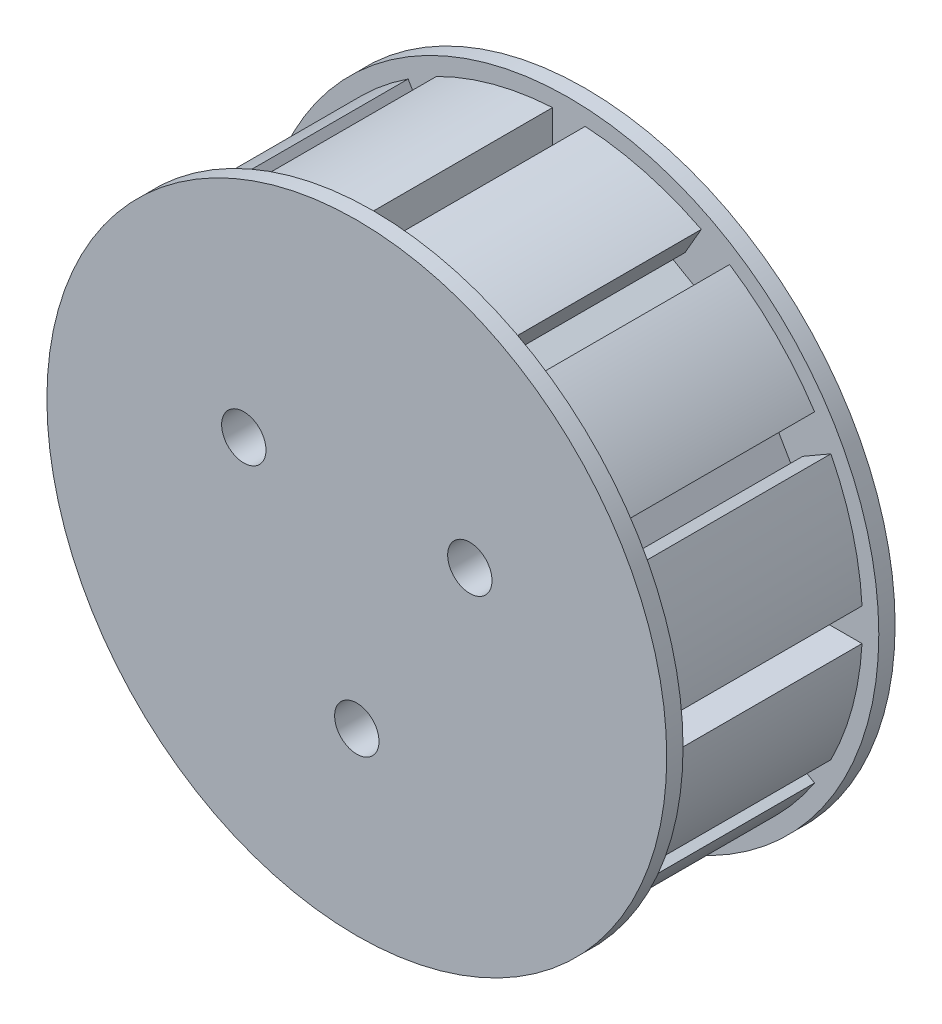
SolidWorks part; units mm, degrees
ref_plane "Front Plane" through (0, 0, 0) normal (0, 0, 1) x (1, 0, 0)
ref_plane "Top Plane" through (0, 0, 0) normal (0, 1, 0) x (1, 0, 0)
ref_plane "Right Plane" through (0, 0, 0) normal (1, 0, 0) x (0, 0, -1)
sketch "Sketch1" plane through (0, 0, 0) normal (0, 0, 1) x (1, 0, 0)
  circle A0 centre (0, 0) radius 28.575
  dimension "D1" = 57.15
extrude "Boss-Extrude1" add sketch "Sketch1" along normal mid plane 19.05
sketch "Sketch2" plane through (0, 0, 0) normal (0, 0, 1) x (1, 0, 0)
  line L0 (-1.5875, 28.5309) -> (-1.5875, 25.3559)
  line L1 (-1.5875, 25.3559) -> (-4.7625, 25.3559)
  line L2 (-4.7625, 25.3559) -> (-4.7625, 23.7684)
  line L3 (-4.7625, 23.7684) -> (4.7625, 23.7684)
  line L4 (4.7625, 23.7684) -> (4.7625, 25.3559)
  line L5 (4.7625, 25.3559) -> (1.5875, 25.3559)
  line L6 (1.5875, 25.3559) -> (1.5875, 28.5309)
  circle A0 centre (0, 0) radius 28.575 construction
  arc A1 (1.5875, 28.5309) -> (-1.5875, 28.5309) centre (0, 0) ccw
  point P11 (0, 23.7684)
  dimension "D1" = 9.525
  dimension "D2" = 3.175
  dimension "D3" = 3.175
  dimension "D4" = 1.5875
extrude "Cut-Extrude1" cut sketch "Sketch2" against normal mid plane 19.05
pattern_circular "CirPattern1" count 12 over 360 about axis through (0, 0, 9.525) along (0, 0, 1) of "Cut-Extrude1"
sketch "Sketch3" plane through (0, 0, -9.525) normal (0, 0, -1) x (-1, 0, 0)
  circle A0 centre (0, 0) radius 30.1625
  arc A1 (-25.5022, 12.8906) -> (-28.5309, 1.5875) centre (0, 0) ccw construction
  dimension "D1" = 1.5875
extrude "Boss-Extrude2" add sketch "Sketch3" along normal blind 1.5875
mirror "Mirror1" about plane through (0, 0, 0) normal (0, 0, 1) of "Boss-Extrude2"
sketch "Sketch4" plane through (0, 0, -11.1125) normal (0, 0, -1) x (-1, 0, 0)
  circle A0 centre (0, -12.7) radius 2.159
  circle A1 centre (-10.9985, 6.35) radius 2.159
  circle A2 centre (10.9985, 6.35) radius 2.159
  point P4 (-13.2921, 7.7818)
  point P5 (0, 0)
  point P9 (0, 0)
  dimension "D1" = 4.318
  dimension "D2" = 12.7
  dimension "D3" = 3
extrude "Cut-Extrude2" cut sketch "Sketch4" against normal through all
